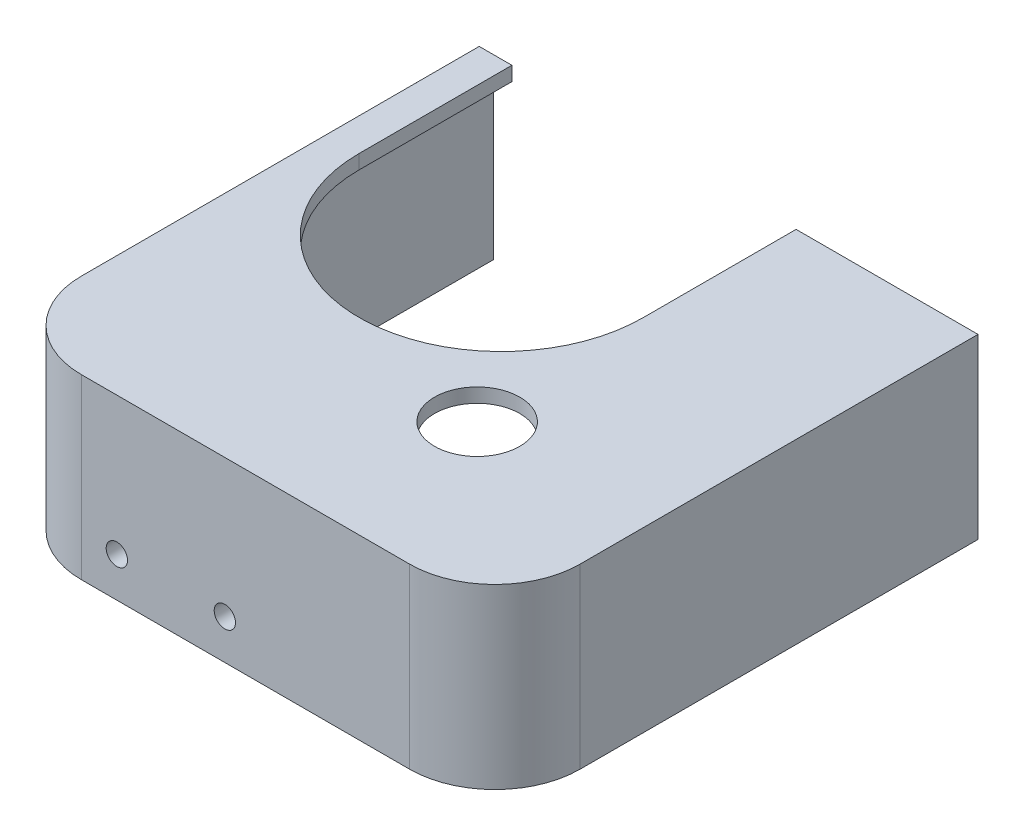
SolidWorks part; units mm, degrees
ref_plane "Front Plane" through (0, 0, 0) normal (0, 0, 1) x (1, 0, 0)
ref_plane "Top Plane" through (0, 0, 0) normal (0, 1, 0) x (1, 0, 0)
ref_plane "Right Plane" through (0, 0, 0) normal (1, 0, 0) x (0, 0, -1)
sketch "Sketch1" plane through (0, 0, 0) normal (0, 0, 1) x (1, 0, 0)
  line L0 (-8.8995, -2) -> (-8.8995, -8) construction
  line L1 (-8.8995, -8) -> (-4.5, -8) construction
  line L2 (-4.5, -8) -> (-4.5, -2) construction
  line L3 (-4.5, -2) -> (-8.8995, -2) construction
  line L4 (-16.5, -2) -> (-16.5, -8) construction
  line L5 (-16.5, -8) -> (-12.1005, -8) construction
  line L6 (-12.1005, -8) -> (-12.1005, -2) construction
  line L7 (-12.1005, -2) -> (-16.5, -2) construction
  line L8 (-8.8995, -2) -> (-8.8995, -8)
  line L9 (-8.8995, -8) -> (-4.5, -8)
  line L10 (-4.5, -8) -> (-4.5, -2)
  line L11 (-4.5, -2) -> (-8.8995, -2)
  line L12 (-16.5, -2) -> (-16.5, -8)
  line L13 (-16.5, -8) -> (-12.1005, -8)
  line L14 (-12.1005, -8) -> (-12.1005, -2)
  line L15 (-12.1005, -2) -> (-16.5, -2)
  circle A0 centre (-6.7, -4.8) radius 0.75 construction
  circle A1 centre (-14.3, -4.8) radius 0.75 construction
  circle A2 centre (-6.7, -4.8) radius 0.75
  circle A3 centre (-14.3, -4.8) radius 0.75
extrude "Boss-Extrude1" add sketch "Sketch1" along normal blind 1.5
sketch "Sketch2" plane through (0, 0, 1.5) normal (0, 0, 1) x (1, 0, 0)
  line L0 (-21.8, -2) -> (-21.8, -14.5)
  line L1 (13, -2) -> (-23.5, -2) construction
  line L2 (-21.8, -14.5) -> (12.3, -14.5)
  line L3 (12.3, -14.5) -> (12.3, -2)
  line L4 (12.3, -2) -> (-21.8, -2)
  circle A0 centre (-6.7, -4.8) radius 0.75 construction
  circle A1 centre (-14.3, -4.8) radius 0.75 construction
  circle A2 centre (-6.7, -4.8) radius 0.75
  circle A3 centre (-14.3, -4.8) radius 0.75
  dimension "D1" = 7.5
  dimension "D2" = 19
  dimension "D3" = 12.5
extrude "Boss-Extrude2" add sketch "Sketch2" against normal blind 1
sketch "Sketch4" plane through (0, -14.5, 0) normal (0, -1, 0) x (1, 0, 0)
  line L0 (-21.8, 0.5) -> (-21.8, -32.5)
  line L1 (-21.8, -32.5) -> (-20.5, -32.5)
  line L2 (12.3, -32.5) -> (12.3, 0.5)
  line L3 (12.3, 0.5) -> (-21.8, 0.5)
  line L4 (-20.5, -21.75) -> (-20.5, -32.5)
  line L5 (-0.5, -21.75) -> (-0.5, -32.5)
  line L6 (-0.5, -32.5) -> (12.3, -32.5)
  arc A0 (-0.5, -21.75) -> (-20.5, -21.75) centre (-10.5, -21.75) ccw
  circle A1 centre (-10.5, -21.75) radius 4 construction
  dimension "D1" = 10
  dimension "D2" = 33
extrude "Boss-Extrude3" add sketch "Sketch4" against normal blind 1
sketch "Sketch5" plane through (-21.8, 0, 0) normal (-1, 0, 0) x (0, 0, 1)
  line L0 (1.5, -2) -> (1.5, -14.5)
  line L1 (1.5, -14.5) -> (-32.5, -14.5)
  line L2 (-32.5, -14.5) -> (-32.5, -2)
  line L3 (0.375, -2) -> (-31.625, -2) construction
  line L4 (-32.5, -2) -> (1.5, -2)
extrude "Boss-Extrude4" add sketch "Sketch5" along normal blind 1
sketch "Sketch6" plane through (12.3, 0, 0) normal (1, 0, 0) x (0, 0, -1)
  line L1 (-1.5, -2) -> (32.5, -2)
  line L2 (31.625, -2) -> (-0.375, -2) construction
  line L3 (32.5, -2) -> (32.5, -13.5) construction
  line L4 (32.5, -2) -> (32.5, -14.5)
  line L6 (-1.5, -2) -> (-1.5, -14.5)
  line L7 (-1.5, -14.5) -> (32.5, -14.5)
  line L8 (32.5, -14.5) -> (32.5, -13.5)
  line L9 (32.5, -13.5) -> (-0.5, -13.5)
  line L10 (-0.5, -13.5) -> (-0.5, -2)
  line L11 (-0.5, -2) -> (-1.5, -2)
  line L12 (-1.5, -2) -> (-1.5, -14.5)
  line L13 (-1.5, -14.5) -> (32.5, -14.5)
  dimension "D1" = 0
extrude "Boss-Extrude5" add sketch "Sketch6" against normal blind 1
sketch "Sketch7" plane through (0, 0, 0.5) normal (0, 0, -1) x (-1, 0, 0)
  line L0 (8.8995, -2) -> (8.8995, -8)
  line L1 (8.8995, -8) -> (12.1005, -8)
  line L2 (12.1005, -8) -> (12.1005, -2)
  line L3 (12.1005, -2) -> (16.5, -2) construction
  line L4 (12.1005, -8) -> (12.1005, -2) construction
  line L5 (12.1005, -2) -> (8.8995, -2)
extrude "Boss-Extrude6" add sketch "Sketch7" along normal blind 2
fillet "Fillet1" radius 2 1 edges at (-10.5, -8, 0.5)
fillet "Fillet2" radius 5 1 edges at (-21.8, -7.75, 0.5)
fillet "Fillet3" radius 6 1 edges at (-22.8, -8.25, 1.5)
fillet "Fillet4" radius 5 1 edges at (11.3, -7.75, 0.5)
fillet "Fillet5" radius 6 1 edges at (12.3, -8.25, 1.5)
sketch "Sketch8" plane through (0, -13.5, 0) normal (0, 1, 0) x (1, 0, 0)
  circle A0 centre (0, 9.555) radius 3
  dimension "D1" = 6
extrude "Cut-Extrude1" cut sketch "Sketch8" against normal blind 2
mirror "Mirror1" about plane through (-10.5, -13.5, -21.75) normal (0, -1, 0) of "Cut-Extrude1", "Fillet5", "Fillet4", "Fillet3", "Fillet2", "Fillet1", "Boss-Extrude6", "Boss-Extrude5", "Boss-Extrude4", "Boss-Extrude3", "Boss-Extrude2", "Boss-Extrude1"
sketch "Sketch9" plane through (0, -2, 0) normal (0, 1, 0) x (1, 0, 0)
  line L16 (-16.8, -1.5) -> (6.3, -1.5)
  line L17 (12.3, 4.5) -> (12.3, 32.5)
  line L18 (12.3, 32.5) -> (11.3, 32.5)
  line L19 (11.3, 32.5) -> (11.3, 4.5)
  line L20 (6.3, -0.5) -> (-4.5, -0.5)
  line L21 (-4.5, -0.5) -> (-4.5, 0)
  line L22 (-4.5, 0) -> (-8.8995, 0)
  line L23 (-8.8995, 0) -> (-8.8995, 1.5)
  line L24 (-8.8995, 1.5) -> (-12.1005, 1.5)
  line L25 (-12.1005, 1.5) -> (-12.1005, 0)
  line L26 (-12.1005, 0) -> (-16.5, 0)
  line L27 (-16.5, 0) -> (-16.5, -0.5)
  line L28 (-16.5, -0.5) -> (-16.8, -0.5)
  line L29 (-21.8, 4.5) -> (-21.8, 32.5)
  line L30 (-21.8, 32.5) -> (-22.8, 32.5)
  line L31 (-22.8, 32.5) -> (-22.8, 4.5)
  line L32 (-16.8, -1.5) -> (6.3, -1.5)
  line L33 (12.3, 4.5) -> (12.3, 32.5)
  line L34 (12.3, 32.5) -> (11.3, 32.5)
  line L35 (11.3, 32.5) -> (11.3, 4.5)
  line L36 (6.3, -0.5) -> (-4.5, -0.5)
  line L37 (-4.5, -0.5) -> (-4.5, 0)
  line L38 (-4.5, 0) -> (-8.8995, 0)
  line L39 (-8.8995, 0) -> (-8.8995, 1.5)
  line L40 (-8.8995, 1.5) -> (-12.1005, 1.5)
  line L41 (-12.1005, 1.5) -> (-12.1005, 0)
  line L42 (-12.1005, 0) -> (-16.5, 0)
  line L43 (-16.5, 0) -> (-16.5, -0.5)
  line L44 (-16.5, -0.5) -> (-16.8, -0.5)
  line L45 (-21.8, 4.5) -> (-21.8, 32.5)
  line L46 (-21.8, 32.5) -> (-22.8, 32.5)
  line L47 (-22.8, 32.5) -> (-22.8, 4.5)
  arc A4 (6.3, -1.5) -> (12.3, 4.5) centre (6.3, 4.5) ccw
  arc A5 (6.3, -0.5) -> (11.3, 4.5) centre (6.3, 4.5) ccw
  arc A6 (-21.8, 4.5) -> (-16.8, -0.5) centre (-16.8, 4.5) ccw
  arc A7 (-22.8, 4.5) -> (-16.8, -1.5) centre (-16.8, 4.5) ccw
  arc A8 (6.3, -1.5) -> (12.3, 4.5) centre (6.3, 4.5) ccw
  arc A9 (6.3, -0.5) -> (11.3, 4.5) centre (6.3, 4.5) ccw
  arc A10 (-21.8, 4.5) -> (-16.8, -0.5) centre (-16.8, 4.5) ccw
  arc A11 (-22.8, 4.5) -> (-16.8, -1.5) centre (-16.8, 4.5) ccw
  dimension "D1" = 0
extrude "Cut-Extrude2" cut sketch "Sketch9" against normal blind 10.5
sketch "Sketch10" plane through (0, -12.5, 0) normal (0, 1, 0) x (1, 0, 0)
  line L7 (-22.8, 32.5) -> (-22.8, 4.5)
  line L13 (-22.8, 32.5) -> (-22.8, 4.5)
  line L15 (-16.8, -1.5) -> (6.3, -1.5)
  line L17 (-16.8, -1.5) -> (6.3, -1.5)
  line L18 (12.3, 4.5) -> (12.3, 32.5)
  line L19 (12.3, 4.5) -> (12.3, 32.5)
  line L24 (12.3, 32.5) -> (-0.5, 32.5)
  line L25 (-0.5, 32.5) -> (-0.5, 21.75)
  line L26 (-20.5, 21.75) -> (-20.5, 32.5)
  line L27 (-20.5, 32.5) -> (-22.8, 32.5)
  line L39 (12.3, 32.5) -> (-0.5, 32.5)
  line L40 (-0.5, 32.5) -> (-0.5, 21.75)
  line L41 (-20.5, 21.75) -> (-20.5, 32.5)
  line L42 (-20.5, 32.5) -> (-22.8, 32.5)
  arc A3 (-22.8, 4.5) -> (-16.8, -1.5) centre (-16.8, 4.5) ccw
  arc A4 (-20.5, 21.75) -> (-0.5, 21.75) centre (-10.5, 21.75) ccw
  arc A7 (-20.5, 21.75) -> (-0.5, 21.75) centre (-10.5, 21.75) ccw
  arc A13 (-22.8, 4.5) -> (-16.8, -1.5) centre (-16.8, 4.5) ccw
  arc A15 (6.3, -1.5) -> (12.3, 4.5) centre (6.3, 4.5) ccw
  arc A16 (6.3, -1.5) -> (12.3, 4.5) centre (6.3, 4.5) ccw
  dimension "D1" = 0
extrude "Cut-Extrude3" [suppressed] cut sketch "Sketch10" against normal blind 1
sketch "Sketch12" plane through (0, -14.5, 0) normal (0, -1, 0) x (1, 0, 0)
  line L7 (-21.8, -4.5) -> (-21.8, -32.5)
  line L8 (-21.8, -32.5) -> (-20.5, -32.5)
  line L9 (-20.5, -32.5) -> (-20.5, -21.75)
  line L10 (-0.5, -21.75) -> (-0.5, -32.5)
  line L11 (-0.5, -32.5) -> (11.3, -32.5)
  line L12 (11.3, -32.5) -> (11.3, -4.5)
  line L13 (6.3, 0.5) -> (-16.8, 0.5)
  line L14 (-21.8, -4.5) -> (-21.8, -32.5)
  line L15 (-21.8, -32.5) -> (-20.5, -32.5)
  line L16 (-20.5, -32.5) -> (-20.5, -21.75)
  line L17 (-0.5, -21.75) -> (-0.5, -32.5)
  line L18 (-0.5, -32.5) -> (11.3, -32.5)
  line L19 (11.3, -32.5) -> (11.3, -4.5)
  line L20 (6.3, 0.5) -> (-16.8, 0.5)
  arc A3 (-0.5, -21.75) -> (-20.5, -21.75) centre (-10.5, -21.75) ccw
  arc A4 (11.3, -4.5) -> (6.3, 0.5) centre (6.3, -4.5) ccw
  arc A5 (-16.8, 0.5) -> (-21.8, -4.5) centre (-16.8, -4.5) ccw
  arc A6 (-0.5, -21.75) -> (-20.5, -21.75) centre (-10.5, -21.75) ccw
  arc A7 (11.3, -4.5) -> (6.3, 0.5) centre (6.3, -4.5) ccw
  arc A8 (-16.8, 0.5) -> (-21.8, -4.5) centre (-16.8, -4.5) ccw
  dimension "D1" = 0
extrude "Cut-Extrude4" cut sketch "Sketch12" against normal blind 1
